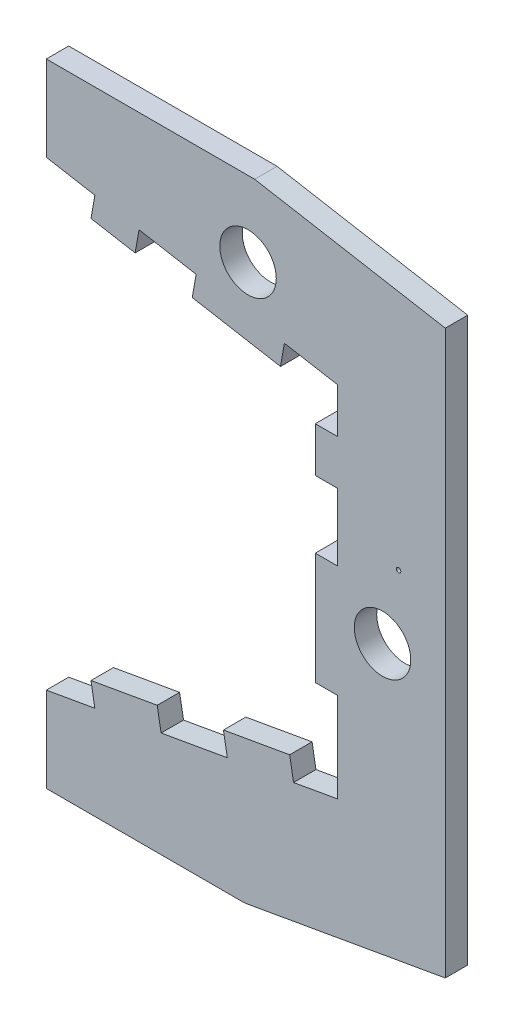
SolidWorks part; units mm, degrees
material "Balsa"
ref_plane "Plan de face" through (0, 0, 0) normal (0, 0, 1) x (1, 0, 0)
ref_plane "Plan de dessus" through (0, 0, 0) normal (0, 1, 0) x (1, 0, 0)
ref_plane "Plan de droite" through (0, 0, 0) normal (1, 0, 0) x (0, 0, -1)
sketch "Esquisse1" plane through (0, 0, 0) normal (0, 0, 1) x (1, 0, 0)
  line L0 (-65, 51.4613) -> (0, 40)
  line L1 (0, 40) -> (0, -40)
  line L2 (-65, -51.4613) -> (0, -40)
  line L3 (-18.4444, 71.4613) -> (-65, 71.4613)
  line L4 (-65, -51.4613) -> (-65, -71.4613)
  line L5 (-20.6259, -71.4613) -> (25, -63.4162)
  line L6 (25, -63.4162) -> (25, 63.8008)
  line L7 (25, 63.8008) -> (-18.4444, 71.4613)
  line L8 (-65, 71.4613) -> (-65, 51.4613)
  line L9 (-18.4444, 71.4613) -> (-20, 53.6808) construction
  line L10 (-65, -71.4613) -> (-20.6259, -71.4613)
  line L11 (0, 0) -> (-84.8855, 0) construction
  circle A0 centre (-20, 53.6808) radius 6.3
  circle A1 centre (10, -5) radius 6.3
  circle A2 centre (13.572, 11) radius 0.5
  point P4 (-30.4766, 71.4613)
  point P13 (-6.595, 69.3719)
  point P15 (-65, -71.4613)
  dimension "D1" = 12.6
  dimension "D13" = 12.6
  dimension "D17" = 1
  dimension "D2" = 10
  dimension "D3" = 20
  dimension "D4" = 80
  dimension "D5" = 65
  dimension "D6" = 100
  dimension "D7" = 100
  dimension "D8" = 20
  dimension "D9" = 27.4016
  dimension "D10" = 90
  dimension "D11" = 10
  dimension "D12" = 35
  dimension "D14" = 100
  dimension "D15" = 13.572
  dimension "D16" = 16
extrude "Boss.-Extru.1" add sketch "Esquisse1" along normal blind 5
sketch "Esquisse4" plane through (0, 0, 5) normal (0, 0, 1) x (1, 0, 0)
  line L0 (0, 40) -> (0, -40) construction
  line L1 (0, 5) -> (-5, 5)
  line L2 (0, 5) -> (0, -20)
  line L3 (0, -20) -> (-5, -20)
  line L4 (-5, 5) -> (-5, -20)
  line L5 (-11.8884, 42.0962) -> (-31.5846, 45.5692)
  line L6 (-11.8884, 42.0962) -> (-12.7566, 37.1722)
  line L7 (-31.5846, 45.5692) -> (-32.4528, 40.6452)
  line L8 (-12.7566, 37.1722) -> (-32.4528, 40.6452)
  line L9 (-65, 51.4613) -> (0, 40) construction
  line L10 (-9.8481, -41.7365) -> (-24.6202, -44.3412)
  line L11 (0, 30) -> (-5, 30)
  line L12 (0, 30) -> (0, 20)
  line L13 (0, 20) -> (-5, 20)
  line L14 (-5, 30) -> (-5, 20)
  line L15 (-9.8481, -41.7365) -> (-10.7163, -36.8124)
  line L16 (-24.6202, -44.3412) -> (-25.4884, -39.4172)
  line L17 (-10.7163, -36.8124) -> (-25.4884, -39.4172)
  line L18 (0, -40) -> (-65, -51.4613) construction
  line L19 (-54.1644, -49.5506) -> (-39.3923, -46.9459)
  line L20 (-54.1644, -49.5506) -> (-55.0327, -44.6266)
  line L21 (-39.3923, -46.9459) -> (-40.2606, -42.0219)
  line L22 (-55.0327, -44.6266) -> (-40.2606, -42.0219)
  line L23 (-44.3163, 47.8142) -> (-54.1644, 49.5506)
  line L24 (-44.3163, 47.8142) -> (-45.1846, 42.8901)
  line L25 (-54.1644, 49.5506) -> (-55.0327, 44.6266)
  line L26 (-45.1846, 42.8901) -> (-55.0327, 44.6266)
  circle A0 centre (10, -5) radius 6.3 construction
  circle A1 centre (-20, 53.6808) radius 6.3 construction
  dimension "D1" = 10
  dimension "D2" = 25
  dimension "D3" = 10
  dimension "D4" = 20
  dimension "D5" = 5
  dimension "D6" = 5
  dimension "D7" = 15
  dimension "D8" = 10
  dimension "D9" = 10
  dimension "D10" = 15
  dimension "D11" = 15
  dimension "D12" = 15
  dimension "D13" = 5
  dimension "D14" = 55
  dimension "D15" = 10
extrude "Boss.-Extru.2" add sketch "Esquisse4" against normal blind 5
sketch "Esquisse5" plane through (0, 0, 5) normal (0, 0, 1) x (1, 0, 0)
  line L0 (-65, 70.4613) -> (-18.5319, 70.4613)
  line L1 (-65, 71.4613) -> (-65, 51.4613) construction
  line L2 (-18.5319, 70.4613) -> (24, 62.9617)
  line L3 (24, 62.9617) -> (24, -62.5771)
  line L4 (24, -62.5771) -> (-20.7134, -70.4613)
  line L5 (-20.7134, -70.4613) -> (-65, -70.4613)
  line L6 (-65, -51.4613) -> (-65, -71.4613) construction
  line L7 (-65, -70.4613) -> (-65, -77.1482)
  line L8 (-65, -77.1482) -> (34.4232, -77.1482)
  line L9 (34.4232, -77.1482) -> (34.4232, 88.8936)
  line L10 (34.4232, 88.8936) -> (-65, 88.8936)
  line L11 (-65, 88.8936) -> (-65, 70.4613)
  line L12 (-18.4444, 71.4613) -> (-65, 71.4613) construction
  line L13 (25, 63.8008) -> (-18.4444, 71.4613) construction
  line L14 (25, -63.4162) -> (25, 63.8008) construction
  line L15 (-20.6259, -71.4613) -> (25, -63.4162) construction
  line L16 (-65, -71.4613) -> (-20.6259, -71.4613) construction
  dimension "D1" = 1
  dimension "D2" = 1
  dimension "D3" = 1
  dimension "D4" = 1
  dimension "D5" = 1
extrude "Enlèv. mat.-Extru.1" cut sketch "Esquisse5" against normal blind 5
